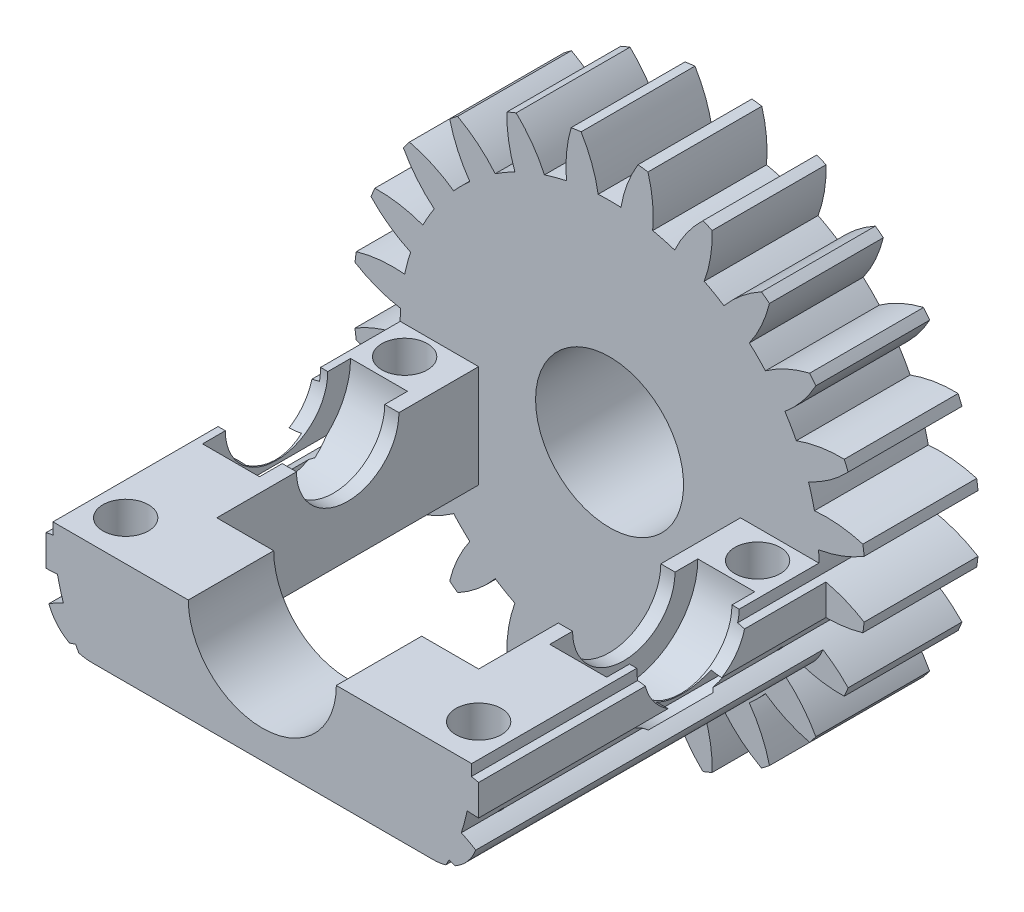
SolidWorks part; units mm, degrees
ref_plane "Front Plane" through (0, 0, 0) normal (0, 0, 1) x (1, 0, 0)
ref_plane "Top Plane" through (0, 0, 0) normal (0, 1, 0) x (1, 0, 0)
ref_plane "Right Plane" through (0, 0, 0) normal (1, 0, 0) x (0, 0, -1)
sketch "Sketch1" plane through (0, 0, 0) normal (0, 1, 0) x (1, 0, 0)
  line L2 (-19, 11.5) -> (-19, -19)
  line L3 (-19, -19) -> (19, -19)
  line L4 (19, 11.5) -> (19, -19)
  line L5 (-11.5, 11.5) -> (19, -19) construction
  line L6 (-19, -19) -> (11.5, 11.5) construction
  line L8 (-11.5, 11.5) -> (-11.5, -11.5)
  line L9 (-11.5, -11.5) -> (11.5, -11.5)
  line L10 (11.5, 11.5) -> (11.5, -11.5)
  line L11 (-11.5, 11.5) -> (11.5, -11.5) construction
  line L12 (-11.5, -11.5) -> (11.5, 11.5) construction
  line L13 (11.5, 11.5) -> (19, 11.5)
  line L14 (-11.5, 11.5) -> (-19, 11.5)
  point P0 (0, 0)
  point P6 (3.75, -3.75)
  dimension "D1" = 38
  dimension "D4" = 23
extrude "Boss-Extrude1" add sketch "Sketch1" along normal blind 9
ref_plane "Plane1" through (15.25, 0, 0) normal (1, 0, 0) x (0, 0, -1)
sketch "Sketch2" plane through (15.25, 0, 0) normal (1, 0, 0) x (0, 0, -1)
  line L1 (-19, 9) -> (-19, 0) construction
  circle A0 centre (0, 9) radius 6.5
  dimension "D1" = 13
  dimension "D2" = 19
extrude "Cut-Extrude1" cut sketch "Sketch2" against normal blind 2.5 and the other way blind 2.5
sketch "Sketch3" plane through (0, 0, 0) normal (1, 0, 0) x (0, 0, -1)
  line L1 (0, 9) -> (0, 0) construction
  circle A0 centre (0, 9) radius 4.5
  dimension "D1" = 9
extrude "Cut-Extrude2" cut sketch "Sketch3" along normal through all
mirror "Mirror1" about plane through (0, 0, 0) normal (1, 0, 0) of "Cut-Extrude1", "Cut-Extrude2"
sketch "Sketch5" plane through (0, 0, -11.5) normal (0, 0, -1) x (-1, 0, 0)
  line L0 (0, 0) -> (0, 9) construction
  circle A0 centre (0, 9) radius 22.5
  dimension "D1" = 45
  dimension "D2" = 9
extrude "Boss-Extrude2" add sketch "Sketch5" along normal blind 10
fillet "Fillet1" radius 4 2 edges at (-19, 0, 3.75) (19, 0, 3.75)
sketch "Sketch4" plane through (0, 0, 0) normal (0, 0, 1) x (1, 0, 0)
  line L0 (-19, 9) -> (19, 9) construction
  circle A0 centre (0, 9) radius 6.5
  dimension "D1" = 13
extrude "Cut-Extrude3" cut sketch "Sketch4" along normal through all both and the other way through all
sketch "Sketch6" plane through (0, 9, 0) normal (0, 1, 0) x (1, 0, 0)
  line L0 (-15.5, 9) -> (15.5, 9) construction
  line L1 (15.5, 9) -> (15.5, -15.5) construction
  line L2 (15.5, -15.5) -> (-15.5, -15.5) construction
  line L3 (-15.5, -15.5) -> (-15.5, 9) construction
  line L4 (-19, -4.5) -> (-19, -19) construction
  line L5 (-19, -19) -> (-6.5, -19) construction
  line L6 (19, -19) -> (19, -4.5) construction
  line L7 (-22.5, 11.5) -> (22.5, 11.5) construction
  circle A0 centre (-15.5, -15.5) radius 2
  circle A1 centre (15.5, -15.5) radius 2
  circle A2 centre (15.5, 9) radius 2
  circle A3 centre (-15.5, 9) radius 2
  dimension "D1" = 3.5
  dimension "D2" = 3.5
  dimension "D3" = 3.5
  dimension "D4" = 2.5
extrude "Cut-Extrude4" cut sketch "Sketch6" against normal through all
sketch "Sketch7" plane through (0, 0, -21.5) normal (0, 0, -1) x (-1, 0, 0)
  line L0 (-12.2364, 25.4283) -> (12.2364, 25.4283) construction
  line L1 (0, 31.3607) -> (0, 9) construction
  line L2 (-2.5, 31.3607) -> (2.5, 31.3607) construction
  arc A0 (-2.5, 31.3607) -> (-1, 27.3607) centre (-12.2364, 25.4283) cw
  circle A1 centre (0, 9) radius 22.5 construction
  arc A2 (2.5, 31.3607) -> (1, 27.3607) centre (12.2364, 25.4283) ccw
  arc A3 (-1, 27.3607) -> (1, 27.3607) centre (0, 9) cw
  arc A4 (-2.5, 31.3607) -> (2.5, 31.3607) centre (0, 9) cw
  point P13 (0, 25.4283)
  dimension "D1" = 2
  dimension "D2" = 4
  dimension "D3" = 5
extrude "Cut-Extrude5" cut sketch "Sketch7" against normal through all
pattern_circular "CirPattern1" count 24 every 15 about axis through (0, 9, -21.5) along (0, 0, 1) of "Cut-Extrude5"
